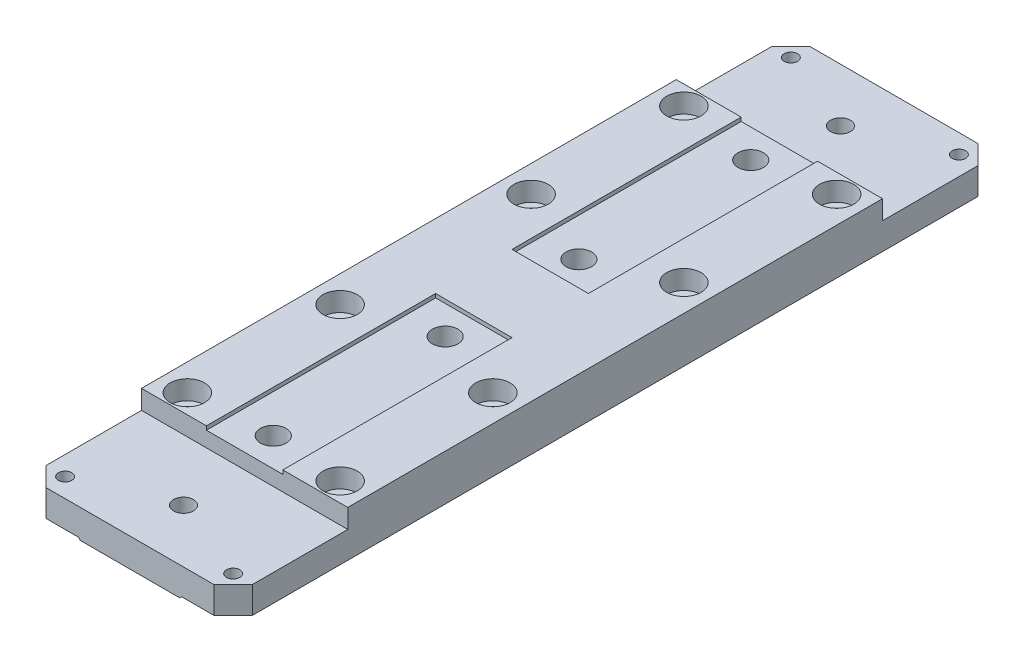
SolidWorks part; units mm, degrees
ref_plane "Płaszczyzna przednia" through (0, 0, 0) normal (0, 0, 1) x (1, 0, 0)
ref_plane "Płaszczyzna górna" through (0, 0, 0) normal (0, 1, 0) x (1, 0, 0)
ref_plane "Płaszczyzna prawa" through (0, 0, 0) normal (1, 0, 0) x (0, 0, -1)
sketch "Sketch1" plane through (0, 0, 0) normal (0, 1, 0) x (1, 0, 0)
  line L0 (0, 100) -> (0, -100) construction
  line L1 (-27, -100) -> (27, -100)
  line L2 (-27, -100) -> (-27, 100)
  line L3 (-27, 100) -> (27, 100)
  line L4 (27, -100) -> (27, 100)
  line L5 (-27, -100) -> (27, 100) construction
  line L6 (-27, 100) -> (27, -100) construction
  line L8 (-20, 25) -> (20, 25) construction
  line L9 (-20, 25) -> (-20, 65) construction
  line L10 (-20, 65) -> (20, 65) construction
  line L11 (20, 25) -> (20, 65) construction
  line L12 (-20, 25) -> (20, 65) construction
  line L13 (-20, 65) -> (20, 25) construction
  line L14 (-20, -25) -> (20, -25) construction
  line L15 (-20, -25) -> (-20, -65) construction
  line L16 (-20, -65) -> (20, -65) construction
  line L17 (20, -25) -> (20, -65) construction
  line L18 (-20, -25) -> (20, -65) construction
  line L19 (-20, -65) -> (20, -25) construction
  circle A0 centre (0, 86) radius 2.6
  circle A1 centre (0, -86) radius 2.6
  circle A2 centre (0, 62.5) radius 3.35
  circle A3 centre (0, 17.5) radius 3.35
  circle A4 centre (0, -17.5) radius 3.35
  circle A5 centre (0, -62.5) radius 3.35
  circle A6 centre (-20, -65) radius 2.6
  circle A7 centre (20, -65) radius 2.6
  circle A8 centre (20, -25) radius 2.6
  circle A9 centre (-20, -25) radius 2.6
  circle A10 centre (-20, 25) radius 2.6
  circle A11 centre (20, 25) radius 2.6
  circle A12 centre (20, 65) radius 2.6
  circle A13 centre (-20, 65) radius 2.6
  point P0 (0, 0)
  point P20 (0, 45)
  point P25 (0, -45)
  dimension "D5" = 5.2
  dimension "D10" = 6.7
  dimension "D17" = 5.2
  dimension "D1" = 200
  dimension "D2" = 54
  dimension "D3" = 14
  dimension "D4" = 14
  dimension "D6" = 45
  dimension "D7" = 45
  dimension "D8" = 37.5
  dimension "D9" = 37.5
  dimension "D11" = 40
  dimension "D12" = 40
  dimension "D13" = 35
  dimension "D14" = 40
  dimension "D15" = 40
  dimension "D16" = 35
extrude "Boss-Extrude1" add sketch "Sketch1" along normal blind 12
sketch "Sketch4" plane through (0, 0, 0) normal (0, 1, 0) x (1, 0, 0)
  circle A0 centre (0, 62.5) radius 5.25
  circle A1 centre (0, 17.5) radius 5.25
  circle A2 centre (0, -17.5) radius 5.25
  circle A3 centre (0, -62.5) radius 5.25
  dimension "D1" = 10.5
  dimension "D2" = 10.5
  dimension "D3" = 10.5
extrude "Cut-Extrude2" cut sketch "Sketch4" along normal blind 6
sketch "Sketch5" plane through (0, 0, 0) normal (0, 1, 0) x (1, 0, 0)
  line L0 (0, 62.5) -> (0, 17.5) construction
  line L1 (0, -17.5) -> (0, -62.5) construction
  line L3 (-10, 70) -> (10, 70)
  line L4 (-10, 70) -> (-10, 10)
  line L5 (-10, 10) -> (10, 10)
  line L6 (10, 70) -> (10, 10)
  line L7 (-10, 70) -> (10, 10) construction
  line L8 (-10, 10) -> (10, 70) construction
  line L9 (-10, -10) -> (10, -10)
  line L10 (-10, -10) -> (-10, -70)
  line L11 (-10, -70) -> (10, -70)
  line L12 (10, -10) -> (10, -70)
  line L13 (-10, -10) -> (10, -70) construction
  line L14 (-10, -70) -> (10, -10) construction
  point P8 (0, 40)
  point P13 (0, -40)
  dimension "D1" = 60
  dimension "D2" = 20
  dimension "D3" = 20
  dimension "D4" = 60
extrude "Cut-Extrude3" cut sketch "Sketch5" against normal blind 1 from surface starting at face at (0, 12, 0)
sketch "Sketch6" plane through (0, 0, 0) normal (0, 1, 0) x (1, 0, 0)
  line L0 (27, 100) -> (-27, 100) construction
  line L1 (-22, 95) -> (22, 95) construction
  line L2 (-22, 95) -> (-22, -95) construction
  line L3 (-22, -95) -> (22, -95) construction
  line L4 (22, 95) -> (22, -95) construction
  line L5 (-22, 95) -> (22, -95) construction
  line L6 (-22, -95) -> (22, 95) construction
  line L7 (27, -100) -> (27, 100) construction
  circle A0 centre (22, 95) radius 1.75
  circle A1 centre (22, -95) radius 1.75
  circle A2 centre (-22, -95) radius 1.75
  circle A3 centre (-22, 95) radius 1.75
  point P0 (0, 0)
  dimension "D3" = 3.5
  dimension "D1" = 5
  dimension "D2" = 5
extrude "Cut-Extrude4" cut sketch "Sketch6" along normal through all both and the other way through all
sketch "Sketch7" plane through (0, 0, 0) normal (0, 1, 0) x (1, 0, 0)
  line L1 (18.5359, 95) -> (20.2679, 92)
  line L2 (20.2679, 92) -> (23.7321, 92)
  line L3 (23.7321, 92) -> (25.4641, 95)
  line L4 (25.4641, 95) -> (23.7321, 98)
  line L5 (23.7321, 98) -> (20.2679, 98)
  line L6 (20.2679, 98) -> (18.5359, 95)
  line L7 (18.5359, -95) -> (20.2679, -98)
  line L8 (20.2679, -98) -> (23.7321, -98)
  line L9 (23.7321, -98) -> (25.4641, -95)
  line L10 (25.4641, -95) -> (23.7321, -92)
  line L11 (23.7321, -92) -> (20.2679, -92)
  line L12 (20.2679, -92) -> (18.5359, -95)
  line L13 (-25.4641, -95) -> (-23.7321, -98)
  line L14 (-23.7321, -98) -> (-20.2679, -98)
  line L15 (-20.2679, -98) -> (-18.5359, -95)
  line L16 (-18.5359, -95) -> (-20.2679, -92)
  line L17 (-20.2679, -92) -> (-23.7321, -92)
  line L18 (-23.7321, -92) -> (-25.4641, -95)
  line L19 (-25.4641, 95) -> (-23.7321, 92)
  line L20 (-23.7321, 92) -> (-20.2679, 92)
  line L21 (-20.2679, 92) -> (-18.5359, 95)
  line L22 (-18.5359, 95) -> (-20.2679, 98)
  line L23 (-20.2679, 98) -> (-23.7321, 98)
  line L24 (-23.7321, 98) -> (-25.4641, 95)
  circle A0 centre (22, 95) radius 3 construction
  circle A1 centre (22, -95) radius 3 construction
  circle A2 centre (-22, -95) radius 3 construction
  circle A3 centre (-22, 95) radius 3 construction
  point P28 (-19.4019, -96.5)
  dimension "D1" = 6
  dimension "D2" = 6
  dimension "D3" = 6
  dimension "D4" = 6
extrude "Cut-Extrude5" cut sketch "Sketch7" along normal blind 3
chamfer "Chamfer2" distance 5 angle 45 4 edges at (27, 6, 100) (27, 6, -100) (-27, 6, -100) (-27, 6, 100)
sketch "Sketch9" plane through (0, 0, 0) normal (0, 1, 0) x (1, 0, 0)
  line L0 (0, -100) -> (0, 100) construction
  line L1 (-22, -100) -> (22, -100) construction
  line L2 (22, 100) -> (-22, 100) construction
  line L4 (13.5, 100) -> (-13.5, 100)
  line L5 (13.5, 100) -> (13.5, -100)
  line L6 (13.5, -100) -> (-13.5, -100)
  line L7 (-13.5, 100) -> (-13.5, -100)
  line L8 (13.5, 100) -> (-13.5, -100) construction
  line L9 (13.5, -100) -> (-13.5, 100) construction
  circle A0 centre (0, -86) radius 2.6
  circle A1 centre (0, -62.5) radius 5.25
  circle A2 centre (0, -17.5) radius 5.25
  circle A3 centre (0, 17.5) radius 5.25
  circle A4 centre (0, 62.5) radius 5.25
  circle A5 centre (0, 86) radius 2.6
  point P6 (0, 0)
  dimension "D1" = 27
extrude "Boss-Extrude3" add sketch "Sketch9" against normal blind 0.5
chamfer "Chamfer3" distance 0.5 angle 45 2 edges at (-13.5, -0.5, 0) (13.5, -0.5, 0)
sketch "Sketch10" plane through (0, 12, 0) normal (0, 1, 0) x (1, 0, 0)
  line L0 (10, 70) -> (-10, 70) construction
  line L1 (27, -70) -> (-27, -70)
  line L2 (27, -70) -> (27, -100)
  line L3 (27, -100) -> (-27, -100)
  line L4 (-27, -70) -> (-27, -100)
  line L5 (27, -70) -> (-27, -100) construction
  line L6 (27, -100) -> (-27, -70) construction
  line L7 (27, 70) -> (-27, 70)
  line L8 (27, 70) -> (27, 100)
  line L9 (27, 100) -> (-27, 100)
  line L10 (-27, 70) -> (-27, 100)
  line L11 (27, 70) -> (-27, 100) construction
  line L12 (27, 100) -> (-27, 70) construction
  line L13 (-10, -70) -> (10, -70) construction
  line L14 (27, -95) -> (27, 95) construction
  line L15 (-27, 95) -> (-27, -95) construction
  line L16 (-22, -100) -> (22, -100) construction
  line L17 (22, 100) -> (-22, 100) construction
  point P0 (0, -85)
  point P5 (0, 85)
extrude "Cut-Extrude6" cut sketch "Sketch10" against normal blind 5
sketch "Sketch11" plane through (0, 0, 0) normal (0, 1, 0) x (1, 0, 0)
  circle A0 centre (20, 65) radius 4.5
  circle A1 centre (-20, 65) radius 4.5
  circle A2 centre (-20, 25) radius 4.5
  circle A3 centre (20, 25) radius 4.5
  circle A4 centre (20, -25) radius 4.5
  circle A5 centre (-20, -25) radius 4.5
  circle A6 centre (-20, -65) radius 4.5
  circle A7 centre (20, -65) radius 4.5
  dimension "D1" = 9
extrude "Cut-Extrude7" cut sketch "Sketch11" against normal blind 5 from surface starting at face at (0, 12, 0)
